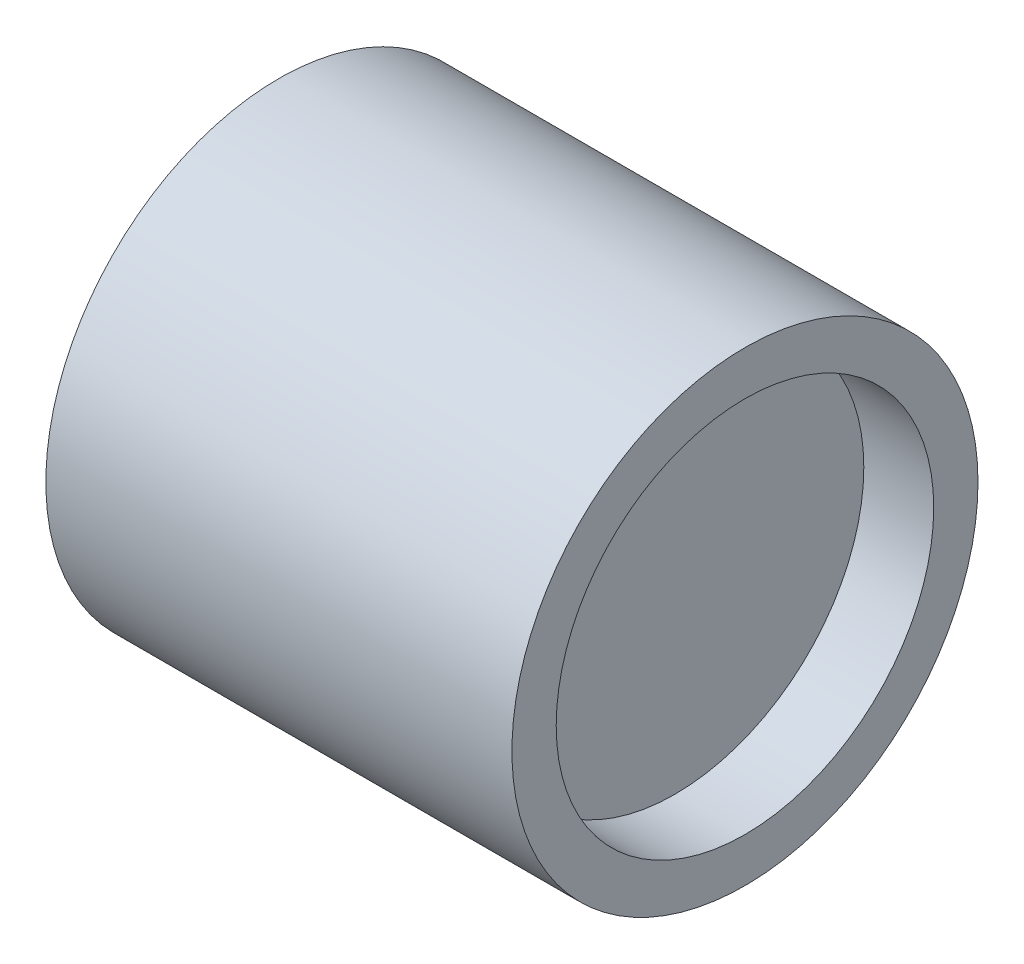
SolidWorks part; units mm, degrees
ref_plane "Front Plane" through (0, 0, 0) normal (1, 0, 0) x (0, 1, 0)
ref_plane "Top Plane" through (0, 0, 0) normal (0, 0, 1) x (0, 1, 0)
ref_plane "Right Plane" through (0, 0, 0) normal (0, 1, 0) x (-1, 0, 0)
sketch "Sketch1" plane through (0, 0, 0) normal (1, 0, 0) x (0, 1, 0)
  circle A0 centre (0, 0) radius 5
  dimension "D1" = 10
extrude "Boss-Extrude1" add sketch "Sketch1" along normal blind 10
sketch "Sketch2" plane through (10, 0, 0) normal (1, 0, 0) x (0, 1, 0)
  circle A0 centre (0, 0) radius 4.05
  dimension "D1" = 8.1
extrude "Cut-Extrude1" cut sketch "Sketch2" against normal blind 1.5
sketch "Sketch4" plane through (0, 0, 0) normal (-1, 0, 0) x (0, -1, 0)
  circle A0 centre (0, 0) radius 2.525
  dimension "D1" = 5.05
extrude "Cut-Extrude2" cut sketch "Sketch4" against normal blind 6
